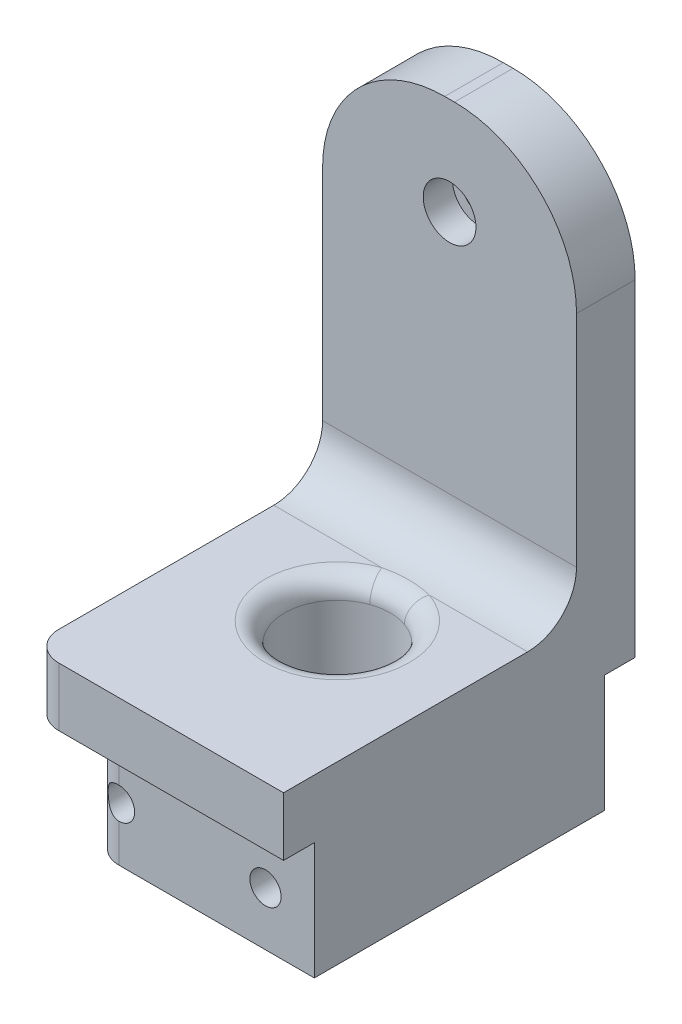
SolidWorks part; units mm, degrees
ref_plane "Front Plane" through (0, 0, 0) normal (0, 0, 1) x (1, 0, 0)
ref_plane "Top Plane" through (0, 0, 0) normal (0, 1, 0) x (1, 0, 0)
ref_plane "Right Plane" through (0, 0, 0) normal (1, 0, 0) x (0, 0, -1)
sketch "Sketch1" plane through (0, -44, 0) normal (0, 1, 0) x (1, 0, 0)
  line L0 (50.2641, 25) -> (50.2641, 28) construction
  line L1 (50.2641, -8) -> (50.2641, 28)
  line L2 (50.2641, -8) -> (27.2641, -8) construction
  line L3 (50.2641, -8) -> (27.2641, -8)
  line L4 (24.2641, -5) -> (24.2641, 25)
  line L5 (27.2641, 28) -> (50.2641, 28)
  arc A0 (27.2641, 28) -> (24.2641, 25) centre (27.2641, 25) ccw construction
  arc A1 (24.2641, -5) -> (27.2641, -8) centre (27.2641, -5) ccw construction
  arc A2 (27.2641, 28) -> (24.2641, 25) centre (27.2641, 25) ccw
  arc A3 (24.2641, -5) -> (27.2641, -8) centre (27.2641, -5) ccw
extrude "Boss-Extrude1" add sketch "Sketch1" along normal blind 6
sketch "Sketch2" plane through (0, -38, 0) normal (0, 1, 0) x (1, 0, 0)
  line L0 (24.2641, 25) -> (24.2641, -5) construction
  line L1 (50.2641, 28) -> (24.2641, 28)
  line L2 (50.2641, 28) -> (50.2641, 22)
  line L3 (50.2641, 22) -> (24.2641, 22)
  line L4 (24.2641, 28) -> (24.2641, 22)
  dimension "D1" = 6
extrude "Boss-Extrude2" add sketch "Sketch2" along normal blind 40
fillet "Fillet1" radius 12.5 2 edges at (24.2641, 2, -25) (50.2641, 2, -25)
sketch "Sketch3" plane through (0, 0, -22) normal (0, 0, 1) x (1, 0, 0)
  circle A0 centre (37.2641, -8) radius 2.7
extrude "Cut-Extrude1" cut sketch "Sketch3" against normal through all
sketch "Sketch4" plane through (0, -44, 0) normal (0, -1, 0) x (1, 0, 0)
  line L3 (50.2641, 4.85) -> (50.2641, -24.85)
  line L6 (50.2641, -24.85) -> (30.2641, -24.85)
  line L7 (27.4141, 2) -> (27.4141, -22)
  line L8 (30.2641, 4.85) -> (50.2641, 4.85)
  arc A4 (27.4141, -22) -> (30.2641, -24.85) centre (30.2641, -22) ccw
  arc A5 (30.2641, 4.85) -> (27.4141, 2) centre (30.2641, 2) ccw
extrude "Boss-Extrude3" add sketch "Sketch4" along normal blind 12
fillet "Fillet2" radius 5 1 edges at (37.2641, -38, -22)
sketch "Sketch5" plane through (0, 0, -24.85) normal (0, 0, -1) x (-1, 0, 0)
  circle A0 centre (-45.2641, -50.5) radius 1.6
  circle A1 centre (-30.2641, -50.5) radius 1.6
extrude "Cut-Extrude2" cut sketch "Sketch5" against normal through all
sketch "Sketch6" plane through (0, -38, 0) normal (0, -1, 0) x (1, 0, 0)
  line L2 (24.2641, -28) -> (27.2641, -28)
  line L3 (24.2641, -25) -> (24.2641, -28)
  line L4 (24.2641, -28) -> (27.2641, -28)
  line L5 (24.2641, -25) -> (24.2641, -28)
  arc A1 (24.2641, -25) -> (27.2641, -28) centre (27.2641, -25) ccw
  arc A2 (24.2641, -25) -> (27.2641, -28) centre (27.2641, -25) ccw
  dimension "D1" = 0
extrude "Cut-Extrude3" cut sketch "Sketch6" against normal through all
sketch "Sketch7" plane through (0, -56, 0) normal (0, -1, 0) x (1, 0, 0)
  line L0 (31.8641, 4.85) -> (30.2641, 4.85) construction
  line L1 (46.8641, 4.85) -> (43.6641, 4.85) construction
  line L2 (31.8641, 4.85) -> (30.2641, 4.85) construction
  line L3 (46.8641, 4.85) -> (43.6641, 4.85) construction
  line L4 (30.2641, 4.85) -> (30.2641, -10.0084) construction
  line L5 (45.2641, 4.85) -> (45.2641, -10.0084) construction
  line L6 (30.2641, -10.0084) -> (45.2641, -10.0084) construction
  circle A0 centre (37.7641, -10.0084) radius 5.4
extrude "Cut-Extrude4" cut sketch "Sketch7" against normal up to surface (18 mm away) up to face at (35.1398, -38, -2.4757)
fillet "Fillet3" radius 2 2 edges at (43.1641, -56, -10.0084) (32.3641, -38, -10.0084)
sketch "Sketch8" plane through (0, 0, -28) normal (0, 0, -1) x (-1, 0, 0)
  circle A0 centre (-37.2641, -8) radius 2.7 construction
  circle A1 centre (-37.2641, -8) radius 2.7
  circle A2 centre (-37.2641, -8) radius 1.6
extrude "Boss-Extrude4" add sketch "Sketch8" against normal blind 3
